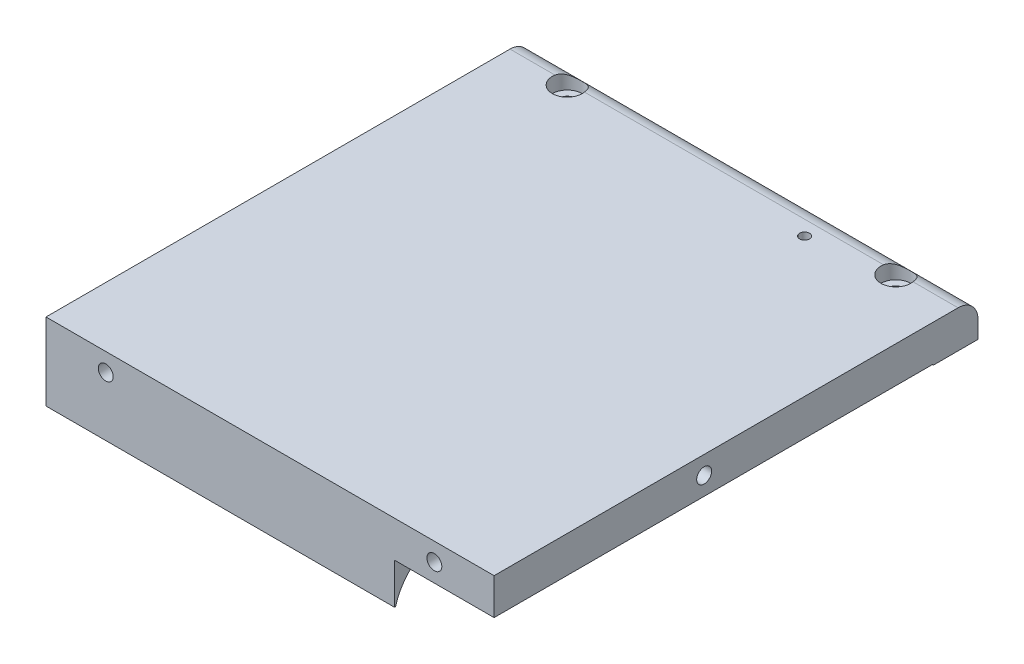
SolidWorks part; units mm, degrees
ref_plane "前视基准面" through (0, 0, 0) normal (0, 0, 1) x (1, 0, 0)
ref_plane "上视基准面" through (0, 0, 0) normal (0, 1, 0) x (1, 0, 0)
ref_plane "右视基准面" through (0, 0, 0) normal (1, 0, 0) x (0, 0, -1)
other "Configuration Table"
sketch "草图1" plane through (0, 0, 0) normal (0, 1, 0) x (1, 0, 0)
  line L1 (0, 0) -> (70, 0)
  line L2 (0, 0) -> (0, 110)
  line L3 (0, 110) -> (70, 110)
  line L4 (70, 0) -> (70, 110)
  dimension "D1" = 110
  dimension "D2" = 70
extrude "凸台-拉伸1" add sketch "草图1" along normal blind 5
sketch "草图2" plane through (70, 0, 0) normal (1, 0, 0) x (0, 0, -1)
  line L0 (12.8087, -13.5) -> (12.8087, 0)
  line L1 (12.8087, -10.5) -> (79.2257, -10.5)
  line L2 (110, 0) -> (110, -2.5)
  line L3 (110, -2.5) -> (89.8087, -2.5)
  line L4 (0, 0) -> (110, 0)
  line L5 (110, 0) -> (110, 5)
  line L6 (110, 5) -> (0, 5)
  line L7 (0, 5) -> (0, 0)
  line L8 (0, 0) -> (110, 0)
  line L9 (110, 0) -> (110, 5)
  line L10 (110, 5) -> (0, 5)
  line L11 (0, 5) -> (0, 0)
  circle A0 centre (89.8087, -13.5) radius 11 construction
  circle A1 centre (67.8087, -13.5) radius 11 construction
  circle A2 centre (45.8087, -13.5) radius 11 construction
  circle A3 centre (23.8087, -13.5) radius 11 construction
  circle A4 centre (89.8087, -13.5) radius 11
  circle A5 centre (67.8087, -13.5) radius 11
  circle A6 centre (45.8087, -13.5) radius 11
  circle A7 centre (23.8087, -13.5) radius 11
  line M8 (0, 0) -> (110, 0)
  dimension "D2" = 10.5
  dimension "D1" = 0
extrude "凸台-拉伸2" add sketch "草图2" against normal up to surface (70 mm away) contours A7 L1 A6 A5 A4 L3 L2 L0 M8 region at (70, -2.7787, -56.9416) up to face at (0, 2.5, -55)
sketch "草图3" plane through (70, 0, 0) normal (1, 0, 0) x (0, 0, -1)
  line L1 (0, 5) -> (12.8087, 5)
  line L2 (0, 5) -> (0, 0)
  line L3 (0, 0) -> (12.8087, 0)
  line L4 (12.8087, 5) -> (12.8087, 0)
extrude "切除-拉伸1" cut sketch "草图3" against normal up to surface (70 mm away) up to face at (0, -3.8018, -49.1544)
sketch "草图4" plane through (70, 0, 0) normal (1, 0, 0) x (0, 0, -1)
  circle A0 centre (23.8087, -13.5) radius 11.2
  arc A1 (34.3917, -10.5) -> (13.2257, -10.5) centre (23.8087, -13.5) ccw construction
  circle A2 centre (45.8087, -13.5) radius 11.2
  circle A3 centre (67.8087, -13.5) radius 11.2
  circle A4 centre (89.8087, -13.5) radius 11.2
  dimension "D1" = 22.4
  dimension "D2" = 4
extrude "切除-拉伸2" cut sketch "草图4" against normal up to next contours A0 | A2 | A4 | A3
sketch "草图5" plane through (70, 0, 0) normal (1, 0, 0) x (0, 0, -1)
  line L0 (110, 5) -> (110, -2.5) construction
  line L1 (12.8087, 5) -> (110, 5)
  line L2 (12.8087, 5) -> (12.8087, -2.3)
  line L3 (12.8087, -2.3) -> (101.0087, -2.3)
  line L4 (110, 5) -> (110, -2.3)
  line L6 (110, -2.5) -> (101.0087, -2.5)
  line L7 (110, -2.5) -> (110, -2.3)
  line L9 (101.0087, -2.5) -> (101.0087, -2.3)
  dimension "D1" = 7.3
  dimension "D2" = 0.2
  dimension "D3" = 8.9913
extrude "凸台-拉伸3" add sketch "草图5" along normal blind 20
sketch "草图6" plane through (0, 0, 0) normal (-1, 0, 0) x (0, 0, 1)
  circle A2 centre (-31, 0.5) radius 1.5
  circle A3 centre (-75, 0.5) radius 1.5
  dimension "D1" = 3
extrude "切除-拉伸3" cut sketch "草图6" against normal blind 10
sketch "草图7" plane through (0, 0, -12.8087) normal (0, 0, 1) x (1, 0, 0)
  circle A2 centre (12, 1.35) radius 1.5
  circle A3 centre (78, 1.35) radius 1.5
  dimension "D1" = 3
extrude "切除-拉伸4" cut sketch "草图7" against normal blind 10
sketch "草图8" plane through (0, 5, 0) normal (0, 1, 0) x (1, 0, 0)
  line L1 (90, 101.0087) -> (90, 110) construction
  line L2 (90, 105.5043) -> (0, 105.5043) construction
  line L3 (0, 110) -> (0, 12.8087) construction
  circle A0 centre (78, 105.5043) radius 1.5
  circle A1 centre (12, 105.5043) radius 1.5
  dimension "D1" = 3
  dimension "D2" = 12
  dimension "D3" = 12
extrude "切除-拉伸5" cut sketch "草图8" against normal up to next
sketch "草图9" plane through (0, 5, 0) normal (0, 1, 0) x (1, 0, 0)
  circle A0 centre (78, 105.5043) radius 3
  circle A1 centre (12, 105.5043) radius 3
  dimension "D1" = 6
extrude "切除-拉伸6" cut sketch "草图9" against normal blind 3
sketch "草图10" plane through (0, 5, 0) normal (0, 1, 0) x (1, 0, 0)
  circle A1 centre (62.109, 103.058) radius 1
extrude "切除-拉伸7" cut sketch "草图10" against normal up to next
fillet "圆角1" radius 4 1 edges at (45, 5, -110)
sketch "草图11" plane through (90, 0, 0) normal (1, 0, 0) x (0, 0, -1)
  line L0 (12.8087, 1.35) -> (55, 1.35) construction
  line L1 (12.8087, 5) -> (12.8087, -2.3) construction
  line L2 (110, -2.5) -> (110, 1) construction
  circle A0 centre (55, 1.35) radius 1.5
  dimension "D1" = 3
  dimension "D2" = 55
extrude "切除-拉伸8" cut sketch "草图11" against normal blind 10
